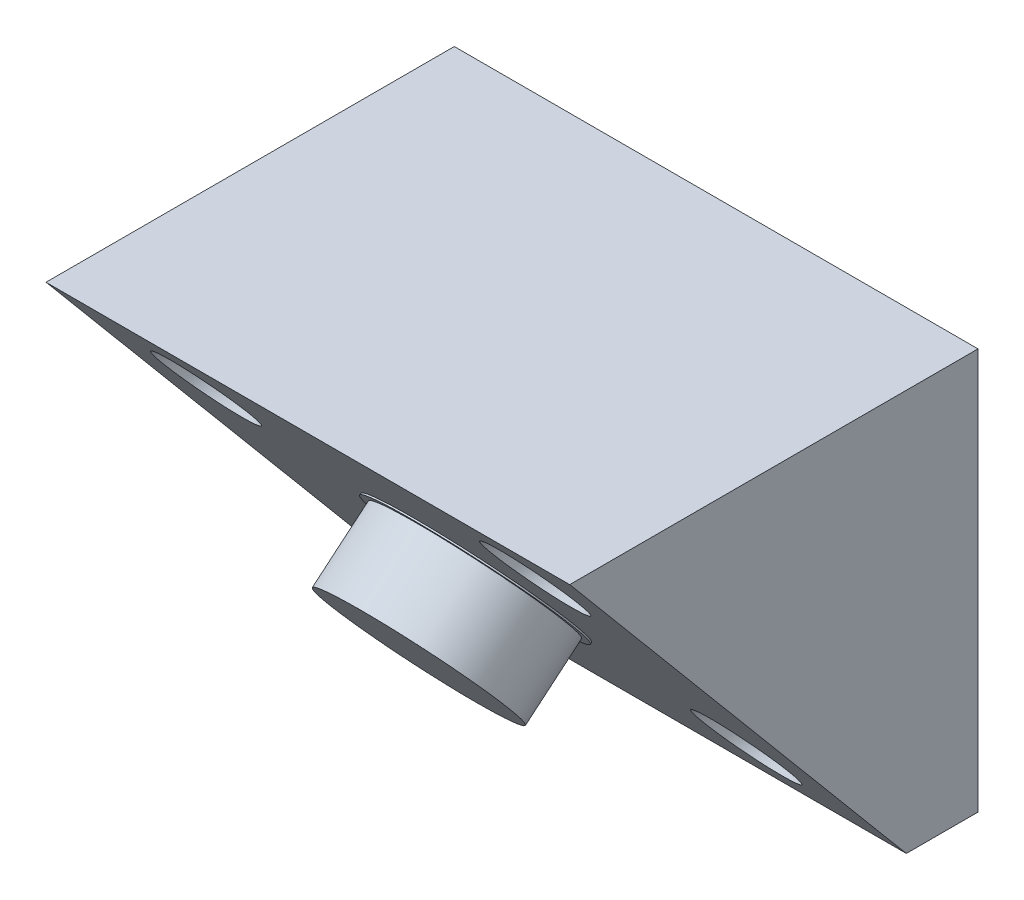
SolidWorks part; units mm, degrees
ref_plane "Ebene vorne" through (0, 0, 0) normal (0, 0, 1) x (1, 0, 0)
ref_plane "Ebene oben" through (0, 0, 0) normal (0, 1, 0) x (1, 0, 0)
ref_plane "Ebene rechts" through (0, 0, 0) normal (1, 0, 0) x (0, 0, -1)
sketch "Skizze1" plane through (0, 0, 0) normal (1, 0, 0) x (0, 0, -1)
  line L0 (0, 0) -> (26.8116, 0)
  line L1 (0, 0) -> (0, 4.79)
  line L2 (0, 4.79) -> (26.8116, 27.2876)
  line L3 (26.8116, 27.2876) -> (26.8116, 0)
  dimension "D1" = 40
  dimension "D2" = 4.79
  dimension "D3" = 35
extrude "Aufsatz-Linear austragen1" add sketch "Skizze1" along normal blind 35
sketch "Skizze3" plane through (0, 2.8109, 2.3586) normal (0, 0.766, 0.6428) x (1, 0, 0)
  line L0 (0, 38.079) -> (35, 3.079) construction
  line L1 (17.5, 20.579) -> (35, 38.079) construction
  circle A0 centre (17.5, 20.579) radius 6
  dimension "D1" = 12
extrude "Aufsatz-Linear austragen2" add sketch "Skizze3" along normal blind 5
sketch "Skizze4" plane through (0, 2.8109, 2.3586) normal (0, 0.766, 0.6428) x (1, 0, 0)
  circle A0 centre (17.5, 20.579) radius 6.5
  dimension "D1" = 13
extrude "Aufsatz-Linear austragen3" add sketch "Skizze4" along normal blind 0.1
ref_plane "Ebene1" through (0, 4.79, 0) normal (0, -1, 0) x (-1, 0, 0)
sketch "Skizze7" plane through (0, 4.79, 0) normal (0, -1, 0) x (-1, 0, 0)
  line L1 (-35, 0) -> (0, 26.8116) construction
  line L2 (-17.5, 13.4058) -> (-17.5, 26.8116) construction
  line L3 (-35, 26.8116) -> (0, 26.8116) construction
  line L4 (-17.5, 13.4058) -> (-35, 13.4058) construction
  line L5 (-35, 0) -> (-35, 26.8116) construction
  circle A0 centre (-28.5, 21.8116) radius 2.85
  circle A1 centre (-6.5, 21.8116) radius 2.85
  circle A2 centre (-6.5, 5) radius 2.85
  circle A3 centre (-28.5, 5) radius 2.85
  dimension "D1" = 5.7
  dimension "D2" = 11
  dimension "D3" = 5
extrude "Schnitt-Linear austragen1" cut sketch "Skizze7" against normal through all
hole_wizard "Ø3.4 (3.4) Durchmesser Bohrung1" positions "3D-Skizze3" profile "Skizze8" hole size "Ø3.4" standard "DIN" end condition up to next
sketch3d "3D-Skizze3"
  line L0 (6.5, 25.4835, -21.8116) -> (6.5, 4.79, -21.8116) construction
  line L1 (6.5, 11.3769, -5) -> (6.5, 4.79, -5) construction
  line L2 (28.5, 11.3769, -5) -> (28.5, 4.79, -5) construction
  line L3 (28.5, 25.4835, -21.8116) -> (28.5, 4.79, -21.8116) construction
  point P0 (6.5, 4.79, -21.8116)
  point P4 (6.5, 4.79, -5)
  point P8 (28.5, 4.79, -5)
  point P12 (28.5, 4.79, -21.8116)
sketch "Skizze8" plane through (6.5, 4.79, -21.8116) normal (1, 0, 0) x (0, 0, 1)
  line L0 (0, 0) -> (0, 4.79)
  line L1 (0, 4.79) -> (1.7, 4.79)
  line L2 (1.7, 4.79) -> (1.7, 0)
  line L5 (1.7, 0) -> (0, 0)
  line L11 (0, -6.35) -> (0, 107.95) construction
  dimension "Bohrerdurchmesser" = 3.4
  dimension "Bohrungstiefe" = 4.79
move or copy body "Körper-Verschieben/Kopieren1" bodies to move or copy 105 copy no rotation origin (0, 13.6438, -13.4058) rotation axis (1, 0, 0) rotation angle 90
